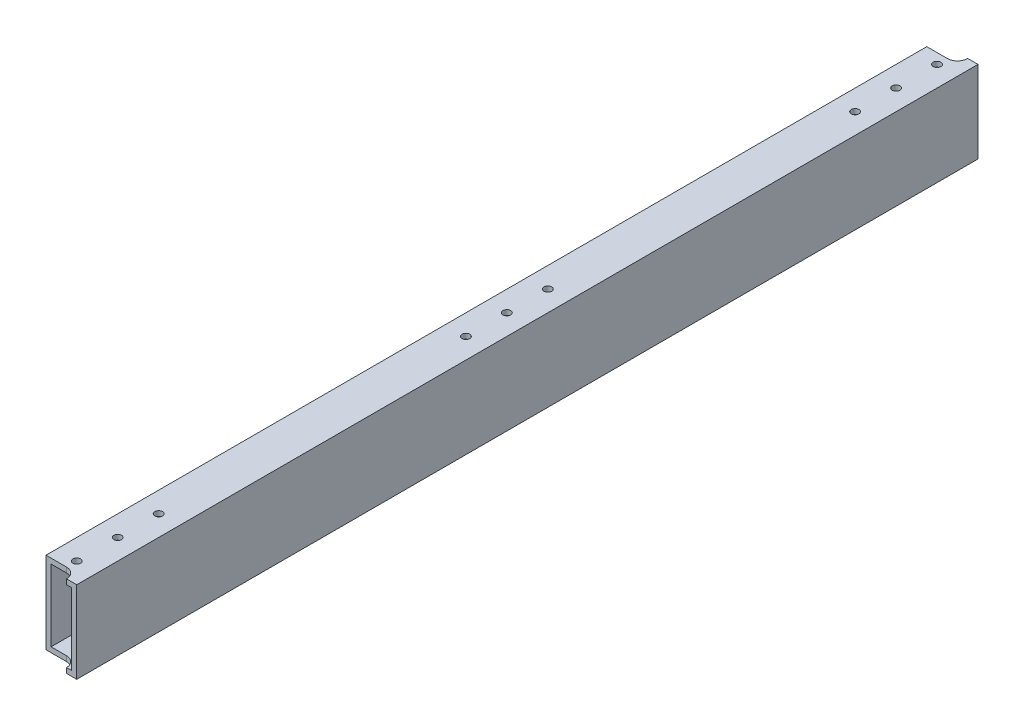
SolidWorks part; units mm, degrees
ref_plane "Front Plane" through (0, 0, 0) normal (0, 0, 1) x (1, 0, 0)
ref_plane "Top Plane" through (0, 0, 0) normal (0, 1, 0) x (1, 0, 0)
ref_plane "Right Plane" through (0, 0, 0) normal (1, 0, 0) x (0, 0, -1)
sketch "Sketch1" plane through (0, 0, 0) normal (0, 0, 1) x (1, 0, 0)
  line L1 (-12.7, 25.4) -> (12.7, 25.4)
  line L2 (-12.7, 25.4) -> (-12.7, -25.4)
  line L3 (-12.7, -25.4) -> (12.7, -25.4)
  line L4 (12.7, 25.4) -> (12.7, -25.4)
  line L5 (0, -25.4) -> (0, 25.4) construction
  line L6 (-12.7, 0) -> (12.7, 0) construction
  point P0 (0, 0)
  dimension "D1" = 25.4
  dimension "D2" = 50.8
extrude "Boss-Extrude1" add sketch "Sketch1" along normal mid plane 558.8
shell "Shell1" thickness 3.175 removed face at (0, 0, -279.4) removed face at (0, 0, 279.4)
sketch "Sketch3" plane through (0, 25.4, 0) normal (0, 1, 0) x (1, 0, 0)
  line L1 (0, 25.4) -> (0, -25.4) construction
  line L3 (6.35, 279.4) -> (-12.7, 279.4)
  line L4 (-12.7, 279.4) -> (-12.7, 273.05)
  line L5 (-12.7, -279.4) -> (-12.7, 279.4) construction
  line L6 (-12.7, 273.05) -> (0, 273.05)
  line L7 (0, 0) -> (77.7351, 0) construction
  line L8 (-12.7, -273.05) -> (0, -273.05)
  line L9 (-12.7, -279.4) -> (-12.7, -273.05)
  line L10 (6.35, -279.4) -> (-12.7, -279.4)
  circle A0 centre (0, 279.4) radius 4.7625 construction
  circle A1 centre (0, 266.7) radius 2.3813
  circle A2 centre (0, 241.3) radius 2.3813
  arc A3 (6.35, 279.4) -> (0, 273.05) centre (0, 279.4) cw
  circle A4 centre (0, 215.9) radius 2.3813
  circle A5 centre (0, -279.4) radius 4.7625 construction
  circle A6 centre (0, -215.9) radius 2.3813
  arc A7 (6.35, -279.4) -> (0, -273.05) centre (0, -279.4) ccw
  circle A8 centre (0, -241.3) radius 2.3813
  circle A9 centre (0, -266.7) radius 2.3813
  circle A10 centre (0, 0) radius 2.3812
  circle A11 centre (0, -25.4) radius 2.3813
  circle A12 centre (0, 25.4) radius 2.3813
  point P35 (0, 0)
  point P38 (0, 0)
  dimension "D1" = 9.525
  dimension "D2" = 4.7625
  dimension "D4" = 25.4
  dimension "D5" = 6.35
  dimension "D6" = 25.4
  dimension "D7" = 25.4
  dimension "D8" = 4.7625
  dimension "D3" = 12.7
extrude "Cut-Extrude1" cut sketch "Sketch3" against normal through all
